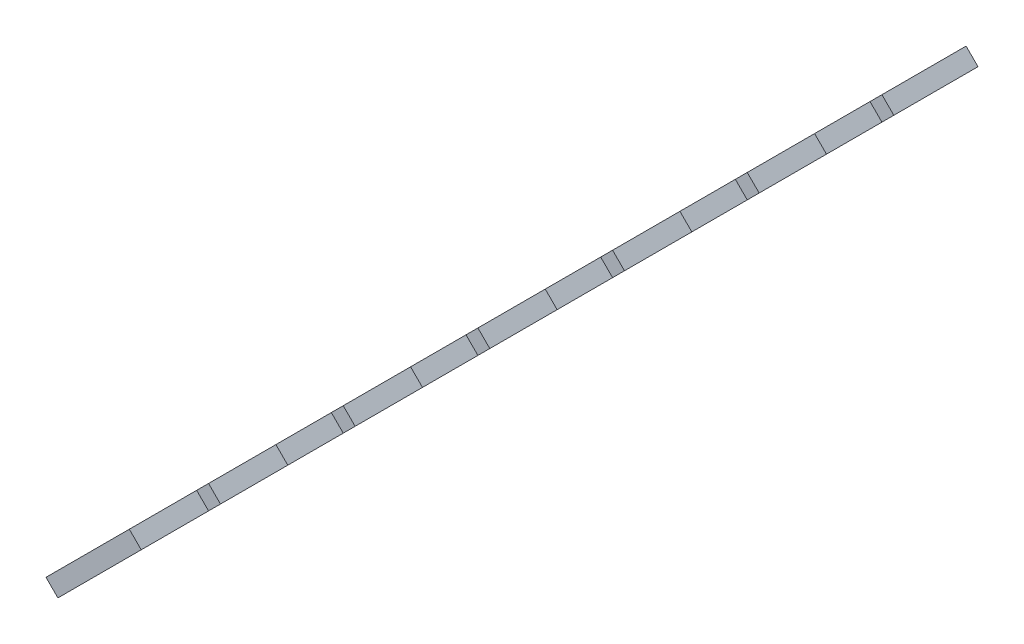
SolidWorks part; units mm, degrees
ref_plane "Front Plane" through (0, 0, 0) normal (0, 0, 1) x (1, 0, 0)
ref_plane "Top Plane" through (0, 0, 0) normal (0, 1, 0) x (1, 0, 0)
ref_plane "Right Plane" through (0, 0, 0) normal (1, 0, 0) x (0, 0, -1)
sketch "Sketch1" plane through (0, 0, 0) normal (0, 0, 1) x (1, 0, 0)
  line L0 (91.6648, 29.3027) -> (52.5461, -9.816) construction
  line L2 (78.5772, 20.7053) -> (74.1015, 16.2295) construction
  line L3 (78.5917, 11.7394) -> (83.0674, 16.2151) construction
  line L4 (39.9621, 9.9289) -> (35.472, 14.4191)
  line L5 (39.9621, 9.9289) -> (71.393, 41.3598)
  line L6 (35.472, 14.4191) -> (66.9029, 45.85)
  line L7 (71.393, 41.3598) -> (66.9029, 45.85)
  line L8 (108.2121, 4.5408) -> (76.7812, -26.8901) construction
  line L9 (76.7812, -26.8901) -> (72.2911, -22.4) construction
  line L10 (103.722, 9.0309) -> (72.2911, -22.4) construction
extrude "Boss-Extrude1" add sketch "Sketch1" along normal up to surface (304.8 mm away)
sketch "Sketch2" plane through (56.3764, 56.3764, 0) normal (0.7071, 0.7071, 0) x (0, 0, -1)
  line L0 (-304.8, -21.2367) -> (0, -21.2367) construction
  line L1 (-279.4, -21.2367) -> (-254, -21.2367)
  line L2 (-279.4, -21.2367) -> (-279.4, -14.8867)
  line L3 (-279.4, -14.8867) -> (-254, -14.8867)
  line L4 (-254, -21.2367) -> (-254, -14.8867)
  line L5 (-304.8, -14.8867) -> (0, -14.8867) construction
  dimension "D1" = 25.4
  dimension "D2" = 25.4
extrude "Boss-Extrude2" add sketch "Sketch2" along normal blind 6.35
pattern_linear "LPattern1" count 6 spacing 50.8 along (0, 0, -1) of "Boss-Extrude2"
sketch "Sketch3" plane through (15.0166, -15.0166, 0) normal (0.7071, -0.7071, 0) x (0, 0, -1)
  circle A0 centre (-273.3375, 57.5033) radius 2.8702
extrude "Cut-Extrude1" cut sketch "Sketch3" against normal up to surface (6.35 mm away) up to face at (66.7302, 45.6773, 155.3308)
sketch "Sketch4" plane through (0, 0, 0) normal (0, 0, -1) x (-1, 0, 0)
  line L0 (-35.472, 14.4191) -> (-39.9621, 9.9289)
  line L1 (-71.393, 50.3401) -> (-35.472, 14.4191) construction
  line L2 (-39.9621, 9.9289) -> (-75.8832, 45.85) construction
  line L3 (-39.9621, 9.9289) -> (-48.9424, 18.9092)
  line L4 (-48.9424, 18.9092) -> (-44.4523, 23.3993)
  line L5 (-44.4523, 23.3993) -> (-35.472, 14.4191)
  dimension "D1" = 12.7
  dimension "D2" = 0
  dimension "D3" = 6.35
extrude "Boss-Extrude3" add sketch "Sketch4" along normal blind 6.35
pattern_linear "LPattern2" count 2 spacing 38.1 along (0.7071, 0.7071, 0) of "Boss-Extrude3"
